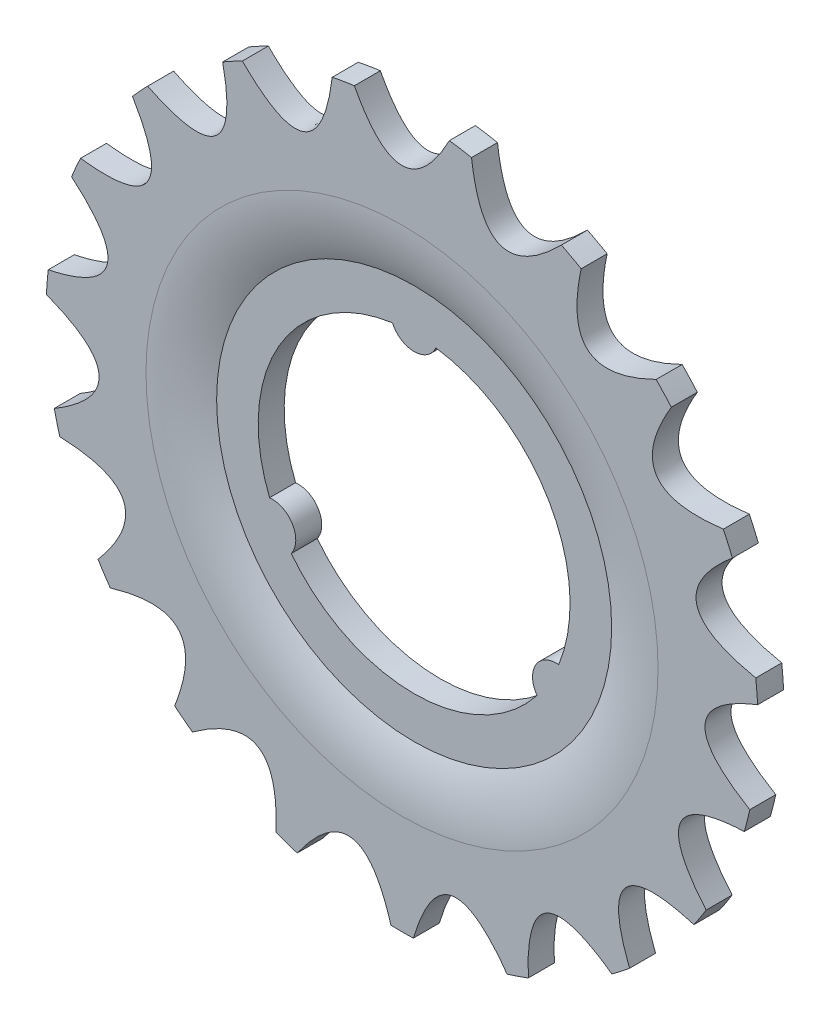
SolidWorks part; units mm, degrees
material "Кованая нержавеющая сталь"
ref_plane "Спереди" through (0, 0, 0) normal (0, 0, 1) x (1, 0, 0)
ref_plane "Сверху" through (0, 0, 0) normal (0, 1, 0) x (1, 0, 0)
ref_plane "Справа" through (0, 0, 0) normal (1, 0, 0) x (0, 0, -1)
sketch "Эскиз1" plane through (0, 0, 0) normal (0, 0, 1) x (1, 0, 0)
  circle A0 centre (0, 0) radius 26
  arc A1 (-5.5, 40.7303) -> (-8.0527, 40.3034) centre (0, 0) ccw
  arc A2 (8.0231, 40.3093) -> (5.4701, 40.7344) centre (0, 0) ccw
  arc A3 (20.6768, 35.5201) -> (18.4001, 36.7511) centre (0, 0) ccw
  arc A4 (31.0899, 26.8818) -> (29.3362, 28.7853) centre (0, 0) ccw
  arc A5 (38.1338, 15.3304) -> (37.0933, 17.7002) centre (0, 0) ccw
  arc A6 (41.0454, 2.1177) -> (40.8307, 4.697) centre (0, 0) ccw
  arc A7 (39.5091, -11.3244) -> (40.1435, -8.8152) centre (0, 0) ccw
  arc A8 (33.6913, -23.5394) -> (35.1061, -21.3722) centre (0, 0) ccw
  arc A9 (24.2226, -33.2035) -> (26.2644, -31.6131) centre (0, 0) ccw
  arc A10 (12.129, -39.2696) -> (14.5766, -38.4283) centre (0, 0) ccw
  arc A11 (-1.279, -41.0801) -> (1.3092, -41.0791) centre (0, 0) ccw
  arc A12 (-14.5484, -38.439) -> (-12.1001, -39.2784) centre (0, 0) ccw
  arc A13 (-26.2412, -31.6324) -> (-24.1982, -33.2213) centre (0, 0) ccw
  arc A14 (-35.0904, -21.3979) -> (-33.674, -23.5642) centre (0, 0) ccw
  arc A15 (-40.137, -8.8447) -> (-39.5008, -11.3534) centre (0, 0) ccw
  arc A16 (-40.8342, 4.667) -> (-41.0469, 2.0876) centre (0, 0) ccw
  arc A17 (-37.1063, 17.673) -> (-38.1451, 15.3024) centre (0, 0) ccw
  arc A18 (-29.3574, 28.7638) -> (-31.1096, 26.859) centre (0, 0) ccw
  arc A19 (-18.4271, 36.7376) -> (-20.7029, 35.5049) centre (0, 0) ccw
  spline S0 degree 2 poles (-5.5, 40.7303) (0.0013, 30.2775) (5.4701, 40.7344) knots 0 0 0 1 1 1
  spline S1 degree 2 poles (8.0231, 40.3093) (9.5704, 27.8702) (18.4001, 36.7511) knots 0 0 0 1 1 1
  spline S2 degree 2 poles (20.6768, 35.5201) (18.1013, 23.2526) (29.3362, 28.7853) knots 0 0 0 1 1 1
  spline S3 degree 2 poles (31.0899, 26.8818) (24.6706, 16.1153) (37.0933, 17.7002) knots 0 0 0 1 1 1
  spline S4 degree 2 poles (38.1338, 15.3304) (28.5665, 7.2315) (40.8307, 4.697) knots 0 0 0 1 1 1
  spline S5 degree 2 poles (41.0454, 2.1177) (29.3668, -2.4358) (40.1435, -8.8152) knots 0 0 0 1 1 1
  spline S6 degree 2 poles (39.5091, -11.3244) (26.9847, -11.8392) (35.1061, -21.3722) knots 0 0 0 1 1 1
  spline S7 degree 2 poles (33.6913, -23.5394) (21.6784, -19.9597) (26.2644, -31.6131) knots 0 0 0 1 1 1
  spline S8 degree 2 poles (24.2226, -33.2035) (14.0229, -25.9172) (14.5766, -38.4283) knots 0 0 0 1 1 1
  spline S9 degree 2 poles (12.129, -39.2696) (4.8478, -29.0661) (1.3092, -41.0791) knots 0 0 0 1 1 1
  spline S10 degree 2 poles (-1.279, -41.0801) (-4.8526, -29.0653) (-12.1001, -39.2784) knots 0 0 0 1 1 1
  spline S11 degree 2 poles (-14.5484, -38.439) (-14.0272, -25.9149) (-24.1982, -33.2213) knots 0 0 0 1 1 1
  spline S12 degree 2 poles (-26.2412, -31.6324) (-21.6817, -19.9561) (-33.674, -23.5642) knots 0 0 0 1 1 1
  spline S13 degree 2 poles (-35.0904, -21.3979) (-26.9866, -11.8348) (-39.5008, -11.3534) knots 0 0 0 1 1 1
  spline S14 degree 2 poles (-40.137, -8.8447) (-29.3672, -2.431) (-41.0469, 2.0876) knots 0 0 0 1 1 1
  spline S15 degree 2 poles (-40.8342, 4.667) (-28.5653, 7.2362) (-38.1451, 15.3024) knots 0 0 0 1 1 1
  spline S16 degree 2 poles (-37.1063, 17.673) (-24.668, 16.1193) (-31.1096, 26.859) knots 0 0 0 1 1 1
  spline S17 degree 2 poles (-29.3574, 28.7638) (-18.0975, 23.2556) (-20.7029, 35.5049) knots 0 0 0 1 1 1
  spline S18 degree 2 poles (-18.4271, 36.7376) (-9.5658, 27.8718) (-8.0527, 40.3034) knots 0 0 0 1 1 1
extrude "Вытянуть1" add sketch "Эскиз1" along normal blind 3
ref_plane "Плоскость1" through (0, 0, 1.6) normal (0, 0, -1) x (-1, 0, 0)
sketch "Эскиз2" plane through (0, 0, 1.6) normal (0, 0, -1) x (-1, 0, 0)
  circle A0 centre (0, 0) radius 22.8
  arc A1 (16.6874, -6.7477) -> (2.5, 17.8255) centre (0, 0) ccw
  arc A2 (2.5, 17.8255) -> (-2.5, 17.8255) centre (0, 18.9352) cw
  arc A3 (-16.6874, -6.7477) -> (-14.1874, -11.0778) centre (-16.3984, -9.4676) cw
  arc A4 (14.1874, -11.0778) -> (16.6874, -6.7477) centre (16.3984, -9.4676) cw
  arc A5 (-2.5, 17.8255) -> (-16.6874, -6.7477) centre (0, 0) ccw
  arc A6 (-14.1874, -11.0778) -> (14.1874, -11.0778) centre (0, 0) ccw
  dimension "D1" = 45.6
  dimension "D2" = 18
  dimension "D3" = 2.7352
  dimension "D4" = 2.7352
  dimension "D5" = 2.7352
  dimension "D6" = 18
  dimension "D7" = 18
  dimension "D8" = 2.5
  dimension "D9" = 14.1874
  dimension "D10" = 16.3984
  dimension "D11" = 2.5
  dimension "D12" = 14.1874
  dimension "D13" = 16.3984
extrude "Вытянуть2" add sketch "Эскиз2" along normal blind 3 separate body
sketch "Эскиз18" plane through (0, 0, 0) normal (0, 1, 0) x (1, 0, 0)
  line L0 (26, -3) -> (22.8, -1.6)
  line L1 (22.8, -1.6) -> (22.8, 1.4)
  line L2 (22.8, 1.4) -> (26, 0)
  line L3 (26, 0) -> (26, -3)
  line L4 (0, 0) -> (0, 11.9347) construction
revolve "Повернуть1" add sketch "Эскиз18" angle 360 about L4
fillet "Скругление8" radius 17 1 edges at (26, 0, 3)
